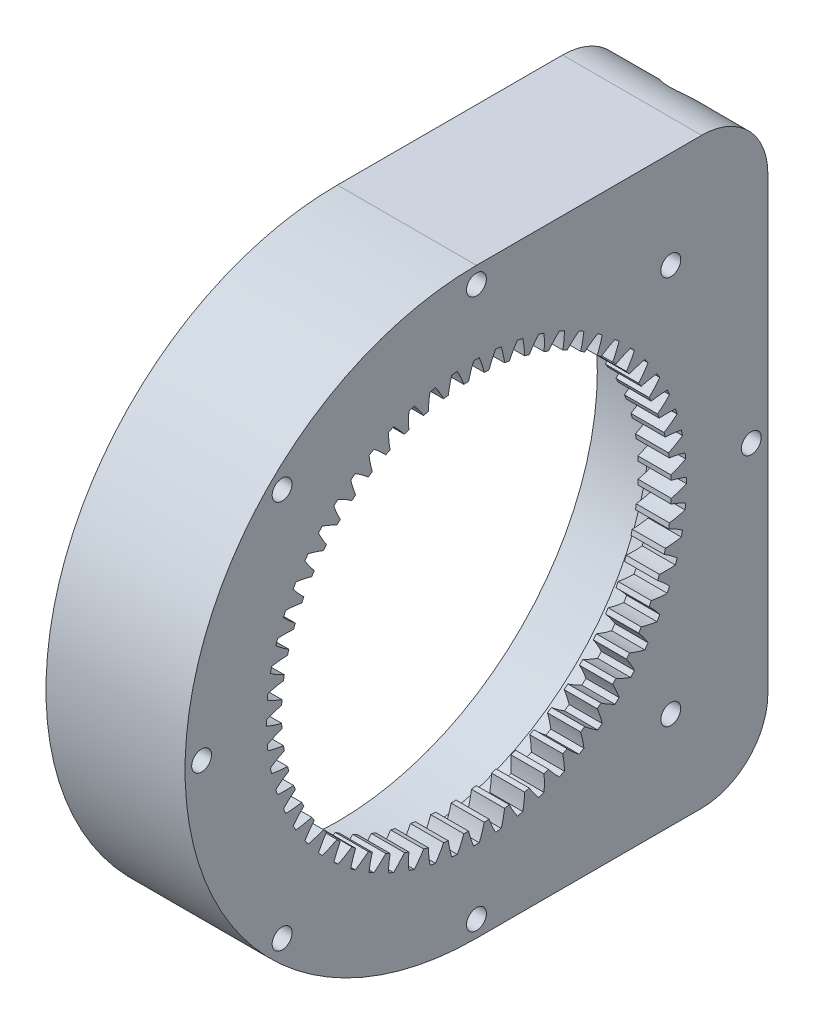
SolidWorks part; units mm, degrees
ref_plane "Plane1" through (0, 0, 0) normal (0, 0, 1) x (1, 0, 0)
ref_plane "Plane2" through (0, 0, 0) normal (0, 1, 0) x (1, 0, 0)
ref_plane "Plane3" through (0, 0, 0) normal (1, 0, 0) x (0, 0, -1)
other "Configuration Table"
sketch "HoldingSke" plane through (0, 0, 0) normal (0, 1, 0) x (1, 0, 0)
  line L0 (0, 0) -> (0.4926, -0.8532)
  line L1 (-15, 0) -> (100, 0) construction
  line L2 (0, 0) -> (-2.1039, 2.3779)
  line L3 (0, 0) -> (-11.863, 4.5341)
  line L4 (0, 0) -> (4.318, 7.479)
  line L5 (0, 0) -> (-23.7986, -8.8762)
  line L6 (0, 0) -> (-10.5278, -7.1032)
  line L7 (-2.1039, 2.3779) -> (3.3635, 27.1825)
  line L8 (-76.2, 3.3929) -> (-54.61, 3.3929)
  line L9 (-67.7845, 28.3722) -> (-49.3413, 33.142)
  line L10 (-76.2, 71.12) -> (104.1128, 71.12)
  line L11 (0, 0) -> (-5, 0)
  line L12 (-76.2, 101.6) -> (-76.162, 101.6)
  line L13 (24.9733, 27.94) -> (52.9518, 28.4284)
  line L14 (24.9733, 27.94) -> (24.9743, 27.94)
  line L15 (24.9733, 27.94) -> (100.4006, 29.5858)
  circle A0 centre (0, 0) radius 44
  circle A1 centre (0, 0) radius 12.7
  circle A2 centre (0, 0) radius 12.7
  dimension "Num_teeth" = 60
  dimension "Pitch_radius" = 180.3128
  dimension "Width" = 5
  dimension "Diameter" = 88
sketch "BasProSke" plane through (0, 0, 0) normal (0, 1, 0) x (1, 0, 0)
  line L0 (-10, 0) -> (60, 0) construction
  line L1 (0, 29.435) -> (0, 44)
  line L2 (0, 29.435) -> (5, 29.435)
  line L3 (5, 29.435) -> (5, 44)
  line L4 (5, 44) -> (0, 44)
  dimension "Thickness" = 5
  dimension "Diameter" = 88
revolve "Base-Revolve" add sketch "BasProSke" angle 360 about L0
sketch "TooCutSke" plane through (0, 0, 0) normal (1, 0, 0) x (0, 0, -1)
  line L3 (0.8921, 30.4369) -> (0.8921, 53.6633) construction
  line L4 (0, 0) -> (0, 59.563) construction
  line L5 (0, 0) -> (-3.576, 68.2339) construction
  line L6 (-13.6269, 25.8543) -> (36.4024, 28.4763) construction
  circle A0 centre (0, 0) radius 30.45 construction
  circle A1 centre (0, 0) radius 31.7197 construction
  circle A2 centre (0, 0) radius 26.5321 construction
  circle A3 centre (0, 0) radius 29.4096 construction
  arc A4 (1.1829, 29.3858) -> (0.4241, 31.7169) centre (-13.6269, 25.8543) ccw
  arc A5 (1.1829, 29.3858) -> (-1.1829, 29.3858) centre (0, 0) ccw
  arc A6 (0.4241, 31.7169) -> (-0.4241, 31.7169) centre (0, 0) ccw
  arc A7 (-0.4241, 31.7169) -> (-1.1829, 29.3858) centre (13.6269, 25.8543) ccw
extrude "ToothCut" cut sketch "TooCutSke" along normal through all
fillet "Breaks" [suppressed] radius 0.1015
fillet "RootFillets" [suppressed] radius 0.2547
pattern_circular "TeethCuts" count 60 every 6 about axis through (-10, 0, 0) along (1, 0, 0) of "RootFillets", "Breaks", "ToothCut"
sketch "Sketch4" plane through (0, 0, 0) normal (-1, 0, 0) x (0, 0, 1)
  circle A0 centre (0, 0) radius 44
  circle A1 centre (0, 0) radius 39.25
  circle A2 centre (0, 0) radius 44 construction
  dimension "D1" = 78.5
extrude "Boss-Extrude3" add sketch "Sketch4" along normal blind 16
sketch "Sketch7" plane through (5, 0, 0) normal (1, 0, 0) x (0, 0, -1)
  line L0 (0, 44) -> (44, 44)
  line L1 (44, 44) -> (44, 0)
  circle A0 centre (0, 0) radius 44 construction
  arc A1 (44, 0) -> (0, 44) centre (0, 0) ccw
extrude "Boss-Extrude5" add sketch "Sketch7" against normal up to surface (21 mm away) up to face at (-16, 0, 44)
sketch "Sketch10" plane through (5, 0, 0) normal (1, 0, 0) x (0, 0, -1)
  line L0 (0, -44) -> (44, -44)
  line L1 (44, -44) -> (44, 0)
  line L2 (44, 0) -> (44, 44) construction
  circle A0 centre (0, 0) radius 44 construction
  arc A1 (0, -44) -> (44, 0) centre (0, 0) ccw
  dimension "D1" = 180
extrude "Boss-Extrude6" add sketch "Sketch10" against normal up to surface (21 mm away) up to face at (-16, 11.6291, -11.6291)
fillet "Fillet1" radius 10 2 edges at (-5.5, 44, -44) (-5.5, -44, -44)
sketch "Sketch14" plane through (0, 0, 0) normal (-1, 0, 0) x (0, 0, 1)
  circle A0 centre (0, 0) radius 37.25
  circle A1 centre (0, 0) radius 39.25 construction
  circle A2 centre (0, 0) radius 39.25
  dimension "D1" = 2
extrude "Boss-Extrude7" add sketch "Sketch14" along normal blind 6
sketch "Sketch15" plane through (0, 0, -44) normal (0, 0, -1) x (-1, 0, 0)
  line L0 (-5, -34) -> (16, -34) construction
  line L1 (16, -44) -> (-5, -44) construction
  line L2 (-5, 44) -> (16, 44) construction
  circle A0 centre (5.5, -38) radius 4.25
  circle A1 centre (5.5, 38) radius 4.25
  point P4 (5.5, -34)
  dimension "D1" = 8.5
  dimension "D2" = 6
  dimension "D3" = 6
extrude "Cut-Extrude1" cut sketch "Sketch15" against normal blind 20
chamfer "Chamfer1" distance 10 angle 1 2 edges at (-9.75, 38, -24) (-9.75, -38, -24) first distance on face at (-5.612, 37.997, -41.83) first distance on face at (-5.388, -37.997, -41.83)
sketch "Sketch16" plane through (-16, 0, 0) normal (-1, 0, 0) x (0, 0, 1)
  circle A0 centre (41.5, 0) radius 1.5
  dimension "D2" = 3
  dimension "D1" = 41.5
extrude "Cut-Extrude3" cut sketch "Sketch16" against normal blind 30
pattern_circular "CirPattern1" count 8 over 360 about axis through (-10, 0, 0) along (-1, 0, 0) of "Cut-Extrude3"
equation "' \"Module@HoldingSke\" = 6.35"
equation "' \"Num_teeth@HoldingSke\" = 24"
equation "' \"Ap@HoldingSke\" =  14.5"
equation "' \"Ap@HoldingSke\" = 14.5"
equation "' \"Width@HoldingSke\" = 12"
equation "' \"Diameter@HoldingSke\" = 8 * 25.4"
equation "' \"Show_teeth@HoldingSke\" = 100"
equation "' \"Backlash@HoldingSke\" = 0.009 * 25.4"
equation "' \"Addendum_fac@HoldingSke\" = 1.0"
equation "' \"Dedendum_fac@HoldingSke\" = 1.25"
equation "' \"Dedendum_add@HoldingSke\" = 0.00005 * 25.4"
equation "' \"Clearance_fac@HoldingSke\" = 0.25"
equation "\"Pitch@HoldingSke\" = 1 / \"Module@HoldingSke\" "
equation "\"Overcut_dia@TooCutSke\" = (\"Num_teeth@HoldingSke\" - 2 * \"Addendum_fac@HoldingSke\") / \"Pitch@HoldingSke\" - 0.002 * 25.4"
equation "\"Pitch_dia@TooCutSke\" = \"Num_teeth@HoldingSke\" / \"Pitch@HoldingSke\""
equation "\"Base_dia@TooCutSke\" = \"Num_teeth@HoldingSke\" / \"Pitch@HoldingSke\" * cos((\"Ap@HoldingSke\"  * 3.14159265 / 180)) * 0.90"
equation "\"Root_dia@TooCutSke\" = \"Num_teeth@HoldingSke\"  / \"Pitch@HoldingSke\" + 2 *  \"Dedendum_fac@HoldingSke\"/ \"Pitch@HoldingSke\" + \"Dedendum_add@HoldingSke\" * 2"
equation "\"Half_ang@TooCutSke\" = 180 / \"Num_teeth@HoldingSke\""
equation "\"Half_CT@TooCutSke\" = \"Num_teeth@HoldingSke\" / \"Pitch@HoldingSke\" * sin((3.14159265 / 2 / \"Num_teeth@HoldingSke\")) / 2 + 10 * \"Backlash@HoldingSke\" / 4"
equation "\"Flank_rad@TooCutSke\" = \"Num_teeth@HoldingSke\" / \"Pitch@HoldingSke\" / 4"
equation "\"Radius@RootFillets\"= \"Clearance_fac@HoldingSke\" / \"Pitch@HoldingSke\" + \"Dedendum_add@HoldingSke\""
equation "\"Break_rad@Breaks\" = 0.02 / \"Pitch@HoldingSke\" * 5"
equation "\"Num_teeth@TeethCuts\" = int( \"Show_teeth@HoldingSke\" ) + 1"
equation "\"Num_teeth@TeethCuts\" = ((sgn( \"Num_teeth@TeethCuts\" - \"Num_teeth@HoldingSke\" )-1)*( \"Num_teeth@TeethCuts\" - \"Num_teeth@HoldingSke\" ))/-2+ \"Num_teeth@HoldingSke\""
equation "\"Num_teeth@TeethCuts\" = ((sgn( \"Num_teeth@TeethCuts\" - 2.0)+1)*( \"Num_teeth@TeethCuts\" - 2.0))/2 +2.0"
equation "\"Angle@TeethCuts\" = 360.0 / \"Num_teeth@HoldingSke\""
equation "\"Diameter@BasProSke\" = \"Num_teeth@HoldingSke\"  / \"Pitch@HoldingSke\" + 2 *  \"Dedendum_fac@HoldingSke\"/ \"Pitch@HoldingSke\" + \"Dedendum_add@HoldingSke\" * 2 + 0.002 * 25.4"
equation "\"Diameter@BasProSke\" = ((sgn( \"Diameter@BasProSke\"  - \"Diameter@HoldingSke\" )+1)*( \"Diameter@BasProSke\"  - \"Diameter@HoldingSke\" ))/2 + \"Diameter@HoldingSke\""
equation "\"Inside_diameter@BasProSke\" =  (\"Num_teeth@HoldingSke\" - 2 * \"Addendum_fac@HoldingSke\") / \"Pitch@HoldingSke\" "
equation "\"Thickness@BasProSke\"  = \"Width@HoldingSke\""
